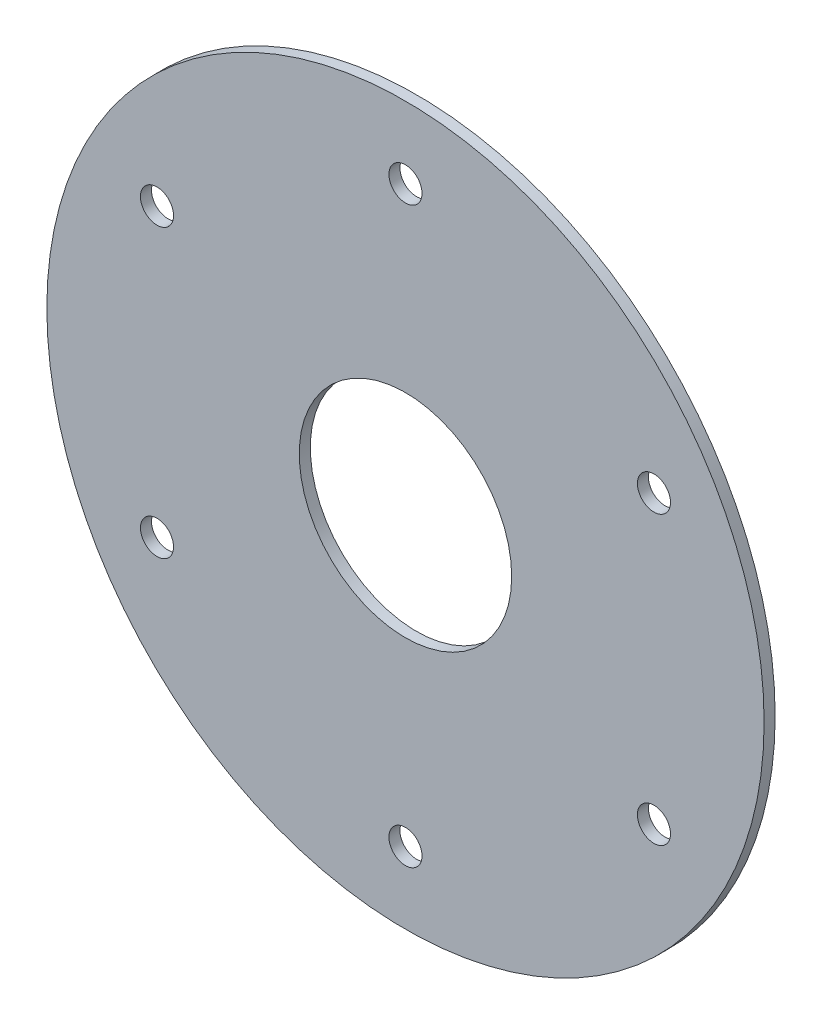
SolidWorks part; units mm, degrees
material "СТ3КП"
ref_plane "Спереди" through (0, 0, 0) normal (0, 0, 1) x (1, 0, 0)
ref_plane "Сверху" through (0, 0, 0) normal (0, 1, 0) x (1, 0, 0)
ref_plane "Справа" through (0, 0, 0) normal (1, 0, 0) x (0, 0, -1)
sketch "Эскиз1" plane through (0, 0, 0) normal (0, 0, 1) x (1, 0, 0)
  line L0 (0, 0) -> (0, 110) construction
  line L1 (0, 0) -> (0, 104) construction
  line L2 (0, 0) -> (90.0666, 52) construction
  line L3 (90.0666, 52) -> (0, 104) construction
  circle A0 centre (0, 0) radius 130
  circle A1 centre (0, 0) radius 38.5 construction
  circle A2 centre (0, 0) radius 38.5
  circle A3 centre (0, 104) radius 6
  circle A4 centre (90.0666, 52) radius 6
  circle A5 centre (90.0666, -52) radius 6
  circle A6 centre (0, -104) radius 6
  circle A7 centre (-90.0666, -52) radius 6
  circle A8 centre (-90.0666, 52) radius 6
  point P0 (97.1179, 41.7894)
  point P14 (0, 0)
  point P25 (0, 0)
  dimension "D1" = 6
base flange "Базовая кромка1" sketch "Эскиз1" thickness 4 reverse thickness direction yes parameters "D1"=1.5
sketch "Сгиб-Линии1" plane through (0, 0, 0) normal (0, 1, 0) x (1, 0, 0)
sketch "Граничная рамка1" plane through (0, 0, 0) normal (0, 1, 0) x (1, 0, 0)
sheet metal parameters "Листовой металл3" thickness 4 parameters "D1"=1.5
flat pattern "Развертка3" [suppressed]
sketch "Сгиб-Линии2" plane through (0, 0, 0) normal (0, 1, 0) x (1, 0, 0)
sketch "Граничная рамка2" [suppressed] plane through (0, 0, 0) normal (0, 1, 0) x (1, 0, 0)
